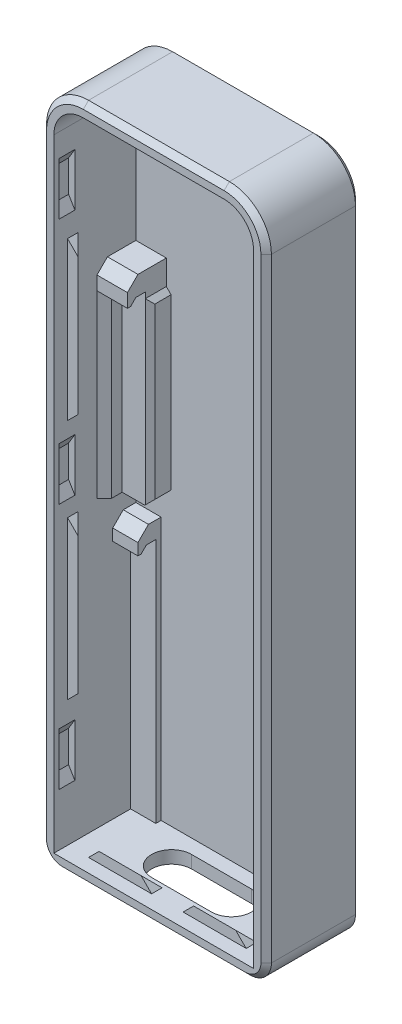
SolidWorks part; units mm, degrees
ref_plane "Ebene vorne" through (0, 0, 0) normal (0, 0, 1) x (1, 0, 0)
ref_plane "Ebene oben" through (0, 0, 0) normal (0, 1, 0) x (1, 0, 0)
ref_plane "Ebene rechts" through (0, 0, 0) normal (1, 0, 0) x (0, 0, -1)
sketch "Skizze1" plane through (0, 0, 0) normal (0, 0, 1) x (1, 0, 0)
  line L0 (0, 0) -> (0, 57.2027) construction
  line L1 (10.7, 32.2) -> (-10.7, 32.2)
  line L2 (10.7, 32.2) -> (10.7, -32.2)
  line L3 (10.7, -32.2) -> (-10.7, -32.2)
  line L4 (-10.7, 32.2) -> (-10.7, -32.2)
  line L5 (10.7, 32.2) -> (-10.7, -32.2) construction
  line L6 (10.7, -32.2) -> (-10.7, 32.2) construction
  line L7 (0, 0) -> (45.1738, 0) construction
  point P0 (0, 0)
  dimension "D1" = 21.4
  dimension "D2" = 64.4
extrude "Aufsatz-Linear austragen1" add sketch "Skizze1" along normal blind 9
fillet "Verrundung1" radius 4 2 edges at (-10.7, 32.2, 4.5) (10.7, 32.2, 4.5)
sketch "Skizze3" plane through (0, 0, 9) normal (0, 0, 1) x (1, 0, 0)
  line L0 (0, 0) -> (0, 33.1072) construction
  line L1 (-10.7, -32.2) -> (10.7, -32.2) construction
  line L2 (-8.6, 13.6) -> (8.6, 13.6)
  line L3 (-8.6, 13.6) -> (-8.6, -5.8)
  line L4 (-8.6, -5.8) -> (8.6, -5.8)
  line L5 (8.6, 13.6) -> (8.6, -5.8)
  line L6 (-8.6, 13.6) -> (8.6, -5.8) construction
  line L7 (-8.6, -5.8) -> (8.6, 13.6) construction
  line L8 (-9.1, -7.8) -> (9.1, -7.8)
  line L9 (-9.1, -7.8) -> (-9.1, -30.8)
  line L10 (-9.1, -30.8) -> (9.1, -30.8)
  line L11 (9.1, -7.8) -> (9.1, -30.8)
  line L12 (-9.1, -7.8) -> (9.1, -30.8) construction
  line L13 (-9.1, -30.8) -> (9.1, -7.8) construction
  line L14 (-2.75, 30.6) -> (2.75, 30.6)
  line L15 (-2.75, 30.6) -> (-2.75, 13.6)
  line L16 (-2.75, 13.6) -> (2.75, 13.6)
  line L17 (2.75, 30.6) -> (2.75, 13.6)
  line L18 (-2.75, 30.6) -> (2.75, 13.6) construction
  line L19 (-2.75, 13.6) -> (2.75, 30.6) construction
  line L20 (4.5, -32.2) -> (-4.5, -32.2)
  line L21 (4.5, -32.2) -> (4.5, -30.8)
  line L22 (4.5, -30.8) -> (-4.5, -30.8)
  line L23 (-4.5, -32.2) -> (-4.5, -30.8)
  line L24 (4.5, -32.2) -> (-4.5, -30.8) construction
  line L25 (4.5, -30.8) -> (-4.5, -32.2) construction
  point P3 (0, 3.9)
  point P8 (0, -19.3)
  point P13 (0, -31.5)
  point P15 (0, 22.1)
  point P23 (0, 0)
  point P24 (9.1, -1.2213)
  point P25 (0, 0)
  dimension "D1" = 17.2
  dimension "D2" = 19.4
  dimension "D3" = 18.2
  dimension "D4" = 23
  dimension "D5" = 5.5
  dimension "D6" = 17
  dimension "D7" = 9
  dimension "D8" = 1.4
  dimension "D9" = 2
shell "Wandung1" thickness 1.2 removed face at (0, 9.6761, 9)
sketch "Skizze4" plane through (0, 0, 1.2) normal (0, 0, 1) x (1, 0, 0)
  line L0 (9.5, -31) -> (9.5, 28.2) construction
  line L1 (9.5, 15.6) -> (6.6, 15.6)
  line L2 (9.5, 15.6) -> (9.5, -3.8)
  line L3 (9.5, -3.8) -> (6.6, -3.8)
  line L4 (6.6, 15.6) -> (6.6, -3.8)
  line L5 (-8.6, -5.8) -> (8.6, -5.8) construction
  line L6 (8.6, 13.6) -> (8.6, -5.8) construction
  line L7 (-8.6, 13.6) -> (8.6, 13.6) construction
  line L8 (0, 0) -> (0, -4.4429) construction
  line L20 (-6.6, 15.6) -> (-6.6, -3.8)
  line L21 (-9.5, -3.8) -> (-6.6, -3.8)
  line L22 (-9.5, 15.6) -> (-9.5, -3.8)
  line L23 (-9.5, 15.6) -> (-6.6, 15.6)
  dimension "D1" = 2
  dimension "D2" = 2
  dimension "D3" = 2
extrude "Aufsatz-Linear austragen3" add sketch "Skizze4" along normal blind 2
sketch "Skizze8" plane through (0, 0, 1.2) normal (0, 0, 1) x (1, 0, 0)
  line L0 (-9.5, -3.8) -> (-9.5, -31) construction
  line L1 (-9.5, -6) -> (-7.1, -6)
  line L2 (-9.5, -6) -> (-9.5, -31)
  line L3 (-9.5, -31) -> (-7.1, -31)
  line L4 (-7.1, -6) -> (-7.1, -31)
  line L5 (-9.5, -31) -> (9.5, -31) construction
  line L6 (-9.1, -7.8) -> (9.1, -7.8) construction
  line L7 (-9.1, -7.8) -> (-9.1, -30.8) construction
  line L8 (0, 0) -> (0, -9.2584) construction
  line L9 (7.1, -6) -> (7.1, -31)
  line L10 (9.5, -31) -> (7.1, -31)
  line L11 (9.5, -6) -> (9.5, -31)
  line L12 (9.5, -6) -> (7.1, -6)
  dimension "D1" = 1.8
  dimension "D2" = 2
extrude "Aufsatz-Linear austragen6" add sketch "Skizze8" along normal blind 0.5
sketch "Skizze5" plane through (0, 0, 3.2) normal (0, 0, 1) x (1, 0, 0)
  line L0 (-9.5, 15.6) -> (-9.5, -3.8) construction
  line L1 (-6.6, 15.6) -> (-9.5, 15.6)
  line L2 (-6.6, 15.6) -> (-6.6, 13.8)
  line L3 (-6.6, 13.8) -> (-9.5, 13.8)
  line L4 (-9.5, 15.6) -> (-9.5, 13.8)
  line L10 (-8.6, 13.6) -> (8.6, 13.6) construction
  line L12 (0, 0) -> (0, -4.7968) construction
  line L17 (9.5, 15.6) -> (9.5, 13.8)
  line L18 (6.6, 13.8) -> (9.5, 13.8)
  line L19 (6.6, 15.6) -> (6.6, 13.8)
  line L20 (6.6, 15.6) -> (9.5, 15.6)
  dimension "D1" = 0.2
extrude "Aufsatz-Linear austragen4" add sketch "Skizze5" along normal blind 0.9
sketch "Skizze9" plane through (0, 0, 1.7) normal (0, 0, 1) x (1, 0, 0)
  line L0 (-7.1, -31) -> (-7.1, -6) construction
  line L1 (-9.5, -6) -> (-7.1, -6)
  line L2 (-9.5, -6) -> (-9.5, -7.6)
  line L3 (-9.5, -7.6) -> (-7.1, -7.6)
  line L4 (-7.1, -6) -> (-7.1, -7.6)
  line L5 (-9.1, -7.8) -> (9.1, -7.8) construction
  line L6 (0, 0) -> (0, -6.4805) construction
  line L7 (7.1, -6) -> (7.1, -7.6)
  line L8 (9.5, -7.6) -> (7.1, -7.6)
  line L9 (9.5, -6) -> (9.5, -7.6)
  line L10 (9.5, -6) -> (7.1, -6)
  dimension "D1" = 0.2
extrude "Aufsatz-Linear austragen7" add sketch "Skizze9" along normal blind 0.9
sketch "Skizze6" plane through (0, 0, 4.1) normal (0, 0, 1) x (1, 0, 0)
  line L5 (-9.5, 28.2) -> (-9.5, -31) construction
  line L6 (-6.6, 15.6) -> (-9.5, 15.6)
  line L7 (-6.6, 15.6) -> (-6.6, 13.3)
  line L8 (-6.6, 13.3) -> (-9.5, 13.3)
  line L9 (-9.5, 15.6) -> (-9.5, 13.3)
  line L10 (0, 0) -> (0, -8.8576) construction
  line L11 (9.5, 15.6) -> (9.5, 13.3)
  line L12 (6.6, 13.3) -> (9.5, 13.3)
  line L13 (6.6, 15.6) -> (6.6, 13.3)
  line L14 (6.6, 15.6) -> (9.5, 15.6)
  line L20 (-9.5, 13.8) -> (-6.6, 13.8) construction
  point P17 (0, 0)
  point P30 (-6.6, 15.6)
  point P32 (-7.1, -5.8)
  dimension "D2" = 0.5
extrude "Aufsatz-Linear austragen5" add sketch "Skizze6" along normal blind 0.8
sketch "Skizze10" plane through (0, 0, 2.6) normal (0, 0, 1) x (1, 0, 0)
  line L0 (-7.1, -31) -> (-7.1, -6) construction
  line L1 (-9.5, -6) -> (-7.1, -6)
  line L2 (-9.5, -6) -> (-9.5, -8.1)
  line L3 (-9.5, -8.1) -> (-7.1, -8.1)
  line L4 (-7.1, -6) -> (-7.1, -8.1)
  line L5 (-9.5, -7.6) -> (-7.1, -7.6) construction
  line L6 (0, 0) -> (0, -8.2451) construction
  line L7 (7.1, -6) -> (7.1, -8.1)
  line L8 (9.5, -8.1) -> (7.1, -8.1)
  line L9 (9.5, -6) -> (9.5, -8.1)
  line L10 (9.5, -6) -> (7.1, -6)
  dimension "D1" = 0.5
extrude "Aufsatz-Linear austragen8" add sketch "Skizze10" along normal blind 0.8
chamfer "Fase2" distance 0.5 angle 45 4 edges at (-8.05, 13.3, 4.1) (8.05, 13.3, 4.1) (-8.3, -8.1, 2.6) (8.3, -8.1, 2.6)
chamfer "Fase3" distance 1 angle 45 4 edges at (8.05, 15.6, 4.9) (-8.05, 15.6, 4.9) (8.3, -6, 3.4) (-8.3, -6, 3.4)
sketch "Skizze7" plane through (0, -32.2, 0) normal (0, -1, 0) x (1, 0, 0)
  line L1 (-9.5, 1.7) -> (-7.1, 1.7) construction
  line L2 (-9.8281, 2.8) -> (6.8205, 2.8) construction
  line L3 (0, 0) -> (0, 9.8373) construction
  line L7 (2.85, 4.45) -> (-2.85, 4.45) construction
  line L8 (2.85, 2.8) -> (-2.85, 2.8) construction
  line L9 (2.85, 6.1) -> (-2.85, 6.1) construction
  line L10 (2.85, 2.55) -> (-2.85, 2.55)
  line L11 (2.85, 6.35) -> (-2.85, 6.35)
  line L12 (-9.5, 1.7) -> (-7.1, 1.7) construction
  arc A2 (2.85, 2.8) -> (2.85, 6.1) centre (2.85, 4.45) ccw construction
  arc A3 (-2.85, 6.1) -> (-2.85, 2.8) centre (-2.85, 4.45) ccw construction
  arc A4 (-2.85, 6.35) -> (-2.85, 2.55) centre (-2.85, 4.45) ccw
  arc A5 (2.85, 2.55) -> (2.85, 6.35) centre (2.85, 4.45) ccw
  point P7 (0, 6.0704)
  point P9 (-3.7555, 4.1)
  point P16 (0, 4.45)
  point P21 (-2.85, 4.1)
  dimension "D2" = 0.25
  dimension "D4" = 9
  dimension "D1" = 1.1
  dimension "D5" = 3.3
extrude "Schnitt-Linear austragen1" cut sketch "Skizze7" against normal up to next
fillet "Verrundung2" radius 2 2 edges at (-10.7, -32.2, 4.5) (10.7, -32.2, 4.5)
sketch "Skizze13" plane through (0, 0, 1.2) normal (0, 0, 1) x (1, 0, 0)
  line L0 (-6.6, -3.8) -> (-6.6, 15.6) construction
  line L1 (-6.6, 13.3) -> (-6.15, 13.3)
  line L2 (-6.6, 13.3) -> (-6.6, -3.8)
  line L3 (-6.6, -3.8) -> (-6.15, -3.8)
  line L4 (-6.15, 13.3) -> (-6.15, -3.8)
  line L5 (0, 0) -> (0, 12.674) construction
  line L6 (0, 0) -> (0, 33.1072) construction
  line L9 (6.15, 13.3) -> (6.15, -3.8)
  line L10 (6.6, -3.8) -> (6.15, -3.8)
  line L11 (6.6, 13.3) -> (6.6, -3.8)
  line L12 (6.6, 13.3) -> (6.15, 13.3)
  line L13 (6.6, 13.3) -> (9.5, 13.3) construction
  line L14 (6.6, 14.6) -> (6.6, 13.3) construction
  line L15 (-9.5, -3.8) -> (-6.6, -3.8) construction
  point P11 (0, 0)
  point P12 (6.6, 13.3)
  point P14 (-6.6, -3.8)
  dimension "D1" = 12.3
extrude "Aufsatz-Linear austragen9" add sketch "Skizze13" along normal blind 2
chamfer "Fase5" distance 0.5 angle 45 4 edges at (6.15, 13.3, 2.2) (6.15, -3.8, 2.2) (-6.15, -3.8, 2.2) (-6.15, 13.3, 2.2)
ref_plane "Ebene1" through (0, 0, 7) normal (0, 0, 1) x (1, 0, 0)
sketch "Skizze14" plane through (0, 0, 7) normal (0, 0, 1) x (1, 0, 0)
  line L0 (0, 0) -> (0, 36.5359) construction
  line L1 (-9.5, 26) -> (-10.1, 25)
  line L2 (-9.5, 28.2) -> (-9.5, 15.6) construction
  line L3 (-10.1, 25) -> (-10.1, 22)
  line L4 (-10.1, 22) -> (-9.5, 21)
  line L5 (-9.5, 28.2) -> (-9.5, -31) construction
  line L6 (-9.5, 21) -> (-9.5, 26)
  line L7 (-9.5, 23.5) -> (-10.907, 23.5) construction
  line L8 (-9.5, 2.5) -> (-10.1, 1.5)
  line L9 (-9.5, -2.5) -> (-9.5, 2.5)
  line L10 (-10.1, 1.5) -> (-10.1, -1.5)
  line L11 (-10.1, -1.5) -> (-9.5, -2.5)
  line L12 (-9.5, -21) -> (-10.1, -22)
  line L13 (-9.5, -26) -> (-9.5, -21)
  line L14 (-10.1, -22) -> (-10.1, -25)
  line L15 (-10.1, -25) -> (-9.5, -26)
  line L16 (6.7, 31) -> (-6.7, 31) construction
  line L17 (-9.5, -31) -> (9.5, -31) construction
  line L18 (9.5, 23.5) -> (10.907, 23.5) construction
  line L19 (10.1, -25) -> (9.5, -26)
  line L20 (10.1, -22) -> (10.1, -25)
  line L21 (9.5, -26) -> (9.5, -21)
  line L22 (9.5, -21) -> (10.1, -22)
  line L23 (10.1, -1.5) -> (9.5, -2.5)
  line L24 (10.1, 1.5) -> (10.1, -1.5)
  line L25 (9.5, -2.5) -> (9.5, 2.5)
  line L26 (9.5, 2.5) -> (10.1, 1.5)
  line L27 (9.5, 21) -> (9.5, 26)
  line L28 (10.1, 22) -> (9.5, 21)
  line L29 (10.1, 25) -> (10.1, 22)
  line L30 (9.5, 26) -> (10.1, 25)
  dimension "D1" = 5
  dimension "D2" = 3
  dimension "D3" = 0.6
  dimension "D4" = 5
  dimension "D5" = 5
extrude "Schnitt-Linear austragen4" cut sketch "Skizze14" along normal blind 1.5
chamfer "Fase7" distance 0.6 angle 45 6 edges at (10.1, -23.5, 8.5) (-10.1, -23.5, 8.5) (-10.1, 0, 8.5) (10.1, 0, 8.5) (10.1, 23.5, 8.5) (-10.1, 23.5, 8.5)
sketch "Skizze15" plane through (0, 0, 3.2) normal (0, 0, 1) x (1, 0, 0)
  line L0 (-9.5, -3.8) -> (-6.65, -3.8) construction
  line L1 (-9.5, 13.8) -> (-8.8, 13.8)
  line L2 (-9.5, 13.8) -> (-9.5, -3.8)
  line L3 (-9.5, -3.8) -> (-8.8, -3.8)
  line L4 (-8.8, 13.8) -> (-8.8, -3.8)
  line L5 (-8.6, 13.6) -> (-8.6, -5.8) construction
  line L6 (0, 0) -> (0, 9.3116) construction
  line L7 (0, 0) -> (0, 33.1072) construction
  line L8 (8.8, 13.8) -> (8.8, -3.8)
  line L9 (9.5, 13.8) -> (9.5, -3.8)
  line L10 (9.5, 13.8) -> (8.8, 13.8)
  line L11 (9.5, -3.8) -> (8.8, -3.8)
  dimension "D1" = 0.2
extrude "Aufsatz-Linear austragen10" add sketch "Skizze15" along normal blind 1
chamfer "Fase8" distance 0.7 angle 45 2 edges at (9.5, 4.95, 4.2) (-9.5, 4.95, 4.2)
chamfer "Fase9" distance 0.45 angle 45 2 edges at (6.15, 4.75, 3.2) (-6.15, 4.75, 3.2)
chamfer "Fase11" distance 0.5 angle 45 16 edges at (-10.7, -1, 9) (-10.1142, -31.6142, 9) (-9.5284, 31.0284, 9) (0, -32.2, 9) (0, 32.2, 9) (10.1142, -31.6142, 9) (9.5284, 31.0284, 9) (10.7, -1, 9) (-10.7, -1, 0) (-10.1142, -31.6142, 0) (-9.5284, 31.0284, 0) (0, -32.2, 0) (0, 32.2, 0) (10.1142, -31.6142, 0) (9.5284, 31.0284, 0) (10.7, -1, 0)
ref_plane "Ebene2" through (0, 0, 7.7) normal (0, 0, 1) x (1, 0, 0)
sketch "Skizze16" plane through (0, 0, 7.7) normal (0, 0, 1) x (1, 0, 0)
  line L0 (9.5, -31) -> (9.5, 28.2) construction
  line L1 (9.5, 19) -> (8.5, 19)
  line L2 (9.5, 19) -> (9.5, 4)
  line L3 (9.5, 4) -> (8.5, 4)
  line L4 (8.5, 19) -> (8.5, 4)
  line L5 (6.7, 31) -> (-6.7, 31) construction
  line L6 (3, 31) -> (7, 31)
  line L7 (3, 31) -> (3, 30)
  line L8 (3, 30) -> (7, 30)
  line L9 (7, 31) -> (7, 30)
  line L10 (-9.5, -31) -> (9.5, -31) construction
  line L11 (9.5, -4) -> (8.5, -4)
  line L12 (9.5, -4) -> (9.5, -19)
  line L13 (9.5, -19) -> (8.5, -19)
  line L14 (8.5, -4) -> (8.5, -19)
  line L15 (7.5, -31) -> (1.5, -31)
  line L16 (7.5, -31) -> (7.5, -30)
  line L17 (7.5, -30) -> (1.5, -30)
  line L18 (1.5, -31) -> (1.5, -30)
  line L19 (0, 0) -> (0, -44.2798) construction
  line L20 (-1.5, -31) -> (-1.5, -30)
  line L21 (-7.5, -30) -> (-1.5, -30)
  line L22 (-7.5, -31) -> (-7.5, -30)
  line L23 (-7.5, -31) -> (-1.5, -31)
  line L24 (-8.5, -4) -> (-8.5, -19)
  line L25 (-9.5, -19) -> (-8.5, -19)
  line L26 (-9.5, -4) -> (-9.5, -19)
  line L27 (-9.5, -4) -> (-8.5, -4)
  line L28 (-7, 31) -> (-7, 30)
  line L29 (-3, 30) -> (-7, 30)
  line L30 (-3, 31) -> (-3, 30)
  line L31 (-3, 31) -> (-7, 31)
  line L32 (-8.5, 19) -> (-8.5, 4)
  line L33 (-9.5, 4) -> (-8.5, 4)
  line L34 (-9.5, 19) -> (-9.5, 4)
  line L35 (-9.5, 19) -> (-8.5, 19)
  line L37 (0, 0) -> (0, 33.1072) construction
  dimension "D1" = 1
  dimension "D2" = 12
  dimension "D3" = 15
  dimension "D4" = 12
  dimension "D5" = 15
  dimension "D6" = 2
  dimension "D7" = 3
  dimension "D8" = 3
  dimension "D9" = 4
extrude "Aufsatz-Linear austragen11" add sketch "Skizze16" against normal blind 1
chamfer "Fase12" distance 1 angle 45 24 edges at (1.5, -30, 7.2) (4.5, -30, 6.7) (7.5, -30, 7.2) (-7.5, -30, 7.2) (-4.5, -30, 6.7) (-1.5, -30, 7.2) (8.5, -19, 7.2) (8.5, -4, 7.2) (8.5, -11.5, 6.7) (8.5, 4, 7.2) (8.5, 19, 7.2) (8.5, 11.5, 6.7) (7, 30, 7.2) (5, 30, 6.7) (3, 30, 7.2) (-8.5, -19, 7.2) (-8.5, -4, 7.2) (-8.5, -11.5, 6.7) (-7, 30, 7.2) (-3, 30, 7.2) (-5, 30, 6.7) (-8.5, 4, 7.2) (-8.5, 19, 7.2) (-8.5, 11.5, 6.7)
equation "\"D1@Skizze1\"=19+2*1.2"
equation "\"D2@Skizze1\"=38+24+2*1.2"
